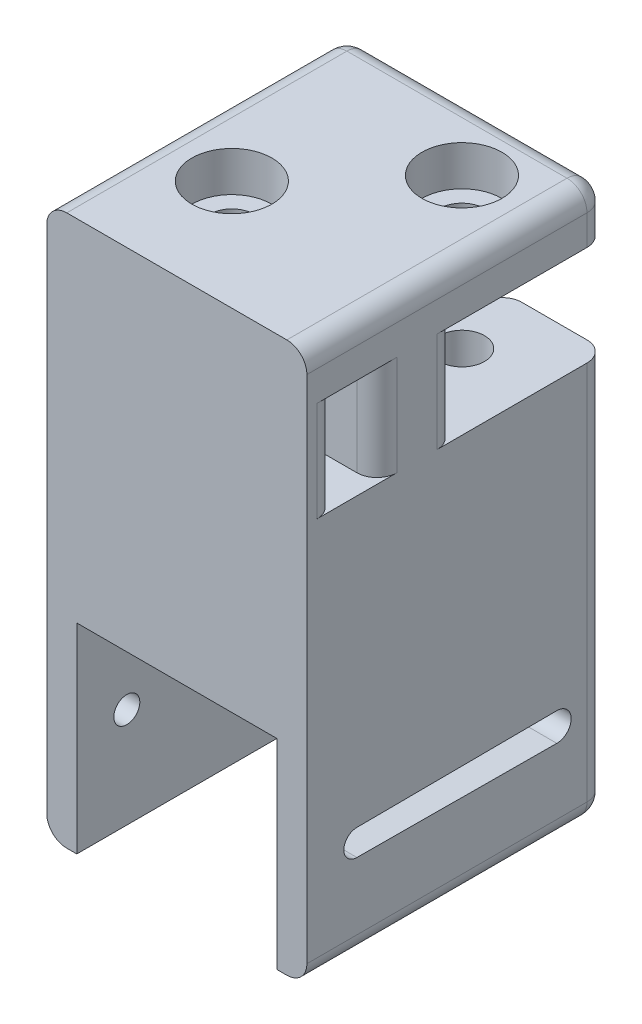
SolidWorks part; units mm, degrees
material "ABS"
ref_plane "Front Plane" through (0, 0, 0) normal (0, 0, 1) x (1, 0, 0)
ref_plane "Top Plane" through (0, 0, 0) normal (0, 1, 0) x (1, 0, 0)
ref_plane "Right Plane" through (0, 0, 0) normal (1, 0, 0) x (0, 0, -1)
sketch "Sketch2" plane through (0, 0, 0) normal (0, 1, 0) x (1, 0, 0)
  line L1 (-10, -15) -> (10, -15)
  line L2 (-10, -15) -> (-10, 15)
  line L3 (-10, 15) -> (10, 15)
  line L4 (10, -15) -> (10, 15)
  line L5 (-10, -15) -> (10, 15) construction
  line L6 (-10, 15) -> (10, -15) construction
  point P0 (0, 0)
  dimension "D1" = 20
  dimension "D2" = 30
extrude "Boss-Extrude1" add sketch "Sketch2" along normal blind 30
sketch "Sketch3" plane through (0, 30, 0) normal (0, 1, 0) x (1, 0, 0)
  line L0 (0, -15) -> (0, 15) construction
  line L1 (-10, -15) -> (10, -15) construction
  line L2 (10, 15) -> (-10, 15) construction
  line L3 (5.5, -1) -> (10, -1)
  line L4 (10, -15) -> (10, 15) construction
  line L6 (-5.5, 11) -> (-10, 11)
  line L7 (-10, 15) -> (-10, -15) construction
  line L8 (-10, 11) -> (-10, -1.3619)
  line L9 (-1.5, -8) -> (-1.5, -1.7446)
  line L10 (1.5, 4) -> (1.5, -2.2554)
  line L11 (-1.5, -8) -> (-1.5, -15)
  line L12 (1.5, -15) -> (1.5, -13.7446)
  line L13 (10, 11) -> (-5.5, 11)
  line L14 (10, 11) -> (10, 8)
  line L15 (10, 8) -> (0.2446, 8)
  line L17 (10, -15) -> (10, -1)
  line L18 (1.5, -15) -> (10, -15)
  line L19 (-5.5, -3) -> (-10, -3)
  line L20 (-10, -3) -> (-10, -1.3619)
  circle A0 centre (5.5, -8) radius 2.25
  circle A1 centre (-5.5, 4) radius 2.25
  arc A2 (5.5, -1) -> (1.5, -13.7446) centre (5.5, -8) ccw
  arc A3 (-5.5, 11) -> (-10, -1.3619) centre (-5.5, 4) cw
  line M1 (10, -15) -> (10, 15)
  line M3 (-10, 15) -> (-10, -15)
  line M4 (-10, -15) -> (10, -15)
  dimension "D3" = 4.5
  dimension "D4" = 4.5
  dimension "D7" = 7
  dimension "D8" = 7
  dimension "D1" = 5.5
  dimension "D2" = 7
  dimension "D5" = 12
  dimension "D6" = 5.5
  dimension "D9" = 3
extrude "Cut-Extrude2" cut sketch "Sketch3" against normal blind 19 contours L0 A2 L3 A0 M1 | A2 L0 | A3 L0 L6 A1 M3 | L0 A3 | L0 A2 L10 A3 | A2 L0 A3 L9 | L0 A2 L11 M4 | L0 L12 A2 M4 | L0 L15 L13 M1 | L15 L0 L13 A3 | L19 A3 M3 region at (-0.8553, 30, 12.8515) region at (0.6574, 30, 14.0101) region at (-0.6059, 30, 8) region at (0.172, 30, 8) region at (-0.8136, 30, 3.1846) region at (0.8136, 30, 0.8154) region at (-0.8157, 30, 0.9677) region at (0.6059, 30, -4) region at (-8.903, 30, 2.5203) region at (-1.3171, 30, -10.2343) region at (5.0068, 30, -9.5019)
sketch "Sketch5" plane through (0, 30, 0) normal (0, 1, 0) x (1, 0, 0)
  line L1 (10, -15) -> (-10, -15)
  line L2 (10, -15) -> (10, 15)
  line L3 (10, 15) -> (-10, 15)
  line L4 (-10, -15) -> (-10, 15)
  line L5 (10, -15) -> (-10, 15) construction
  line L6 (10, 15) -> (-10, -15) construction
  point P0 (0, 0)
extrude "Boss-Extrude2" add sketch "Sketch5" along normal blind 5
sketch "Sketch6" [suppressed] plane through (0, 30, 0) normal (0, -1, 0) x (1, 0, 0)
  line L3 (-1.5, 15) -> (10, 15) construction
  line L8 (1.5, 2.2554) -> (1.5, 15)
  line L9 (-1.5, 15) -> (10, 15) construction
  line L10 (1.5, 15) -> (10, 15)
  line L11 (10, 15) -> (10, 1)
  line L12 (10, 1) -> (5.5, 1)
  line L13 (5.5, 1) -> (10, 1) construction
  circle A0 centre (5.5, 8) radius 2.2812
  arc A1 (5.5, 1) -> (1.5, 2.2554) centre (5.5, 8) cw
extrude "Boss-Extrude3" [suppressed] add sketch "Sketch6" along normal blind 9
sketch "Sketch7" [suppressed] plane through (0, 11, 0) normal (0, 1, 0) x (1, 0, 0)
  line L0 (0.2446, 8) -> (-10, 8)
  line L1 (-5.5, -3) -> (-10, -3)
  line L2 (-10, 11) -> (-10, -3) construction
  line L3 (-1.5, -15) -> (-1.5, -1.7446) construction
  line L4 (-1.5, -1.7446) -> (-1.5, -8)
  line L5 (1.5, -2.2554) -> (1.5, 4)
  line L6 (1.5, 4) -> (1.5, -2.2554) construction
  line L7 (-10, 8) -> (-10, -3)
  arc A0 (0.2446, 8) -> (1.5, 4) centre (-5.5, 4) cw
  arc A1 (-1.5, -1.7446) -> (-5.5, -3) centre (-5.5, 4) cw
  arc A2 (-5.5, -3) -> (-1.5, -1.7446) centre (-5.5, 4) ccw construction
  arc A3 (1.5, -2.2554) -> (-1.5, -8) centre (5.5, -8) ccw
  circle A4 centre (-5.5, 4) radius 2.25
  arc A5 (-5.5, -3) -> (-1.5, -1.7446) centre (-5.5, 4) ccw construction
  arc M1 (-5.5, -3) -> (-1.5, -1.7446) centre (-5.5, 4) ccw
  line M2 (-1.5, -1.7446) -> (-1.5, -15)
  line M7 (1.5, -2.2554) -> (1.5, 4)
  arc M8 (1.5, 4) -> (0.2446, 8) centre (-5.5, 4) ccw
  line M9 (0.2446, 8) -> (10, 8)
  line M11 (10, 11) -> (-10, 11)
  line M12 (-10, 11) -> (-10, -3)
  circle M14 centre (-5.5, 4) radius 2.25
extrude "Boss-Extrude4" [suppressed] add sketch "Sketch7" along normal blind 9 contours A3 L0 M7 M8 M9 M11 M12 M1 M2 M14
sketch "Sketch15" [suppressed] plane through (0, 30, 0) normal (0, -1, 0) x (1, 0, 0)
  line L0 (10, -11) -> (-10, -11) construction
  line L5 (10, -8) -> (10, -11)
  line L6 (10, -11) -> (-5.5, -11)
  line L7 (0.2446, -8) -> (10, -8)
  arc A0 (0.2446, -8) -> (-5.5, -11) centre (-5.5, -4) cw
extrude "Boss-Extrude6" [suppressed] add sketch "Sketch15" along normal blind 9
sketch "Sketch16" plane through (0, 11, 0) normal (0, 1, 0) x (1, 0, 0)
  line L0 (10, -15) -> (10, -1)
  line L1 (10, -1) -> (5.5, -1)
  line L2 (10, -15) -> (1.5, -15)
  line L3 (-1.5, -15) -> (10, -15) construction
  line L4 (1.5, -15) -> (1.5, -2.2554)
  circle A0 centre (5.5, -8) radius 2.25
  arc A1 (5.5, -1) -> (1.5, -2.2554) centre (5.5, -8) ccw construction
  arc A2 (1.5, -2.2554) -> (5.5, -1) centre (5.5, -8) cw
  arc M2 (5.5, -1) -> (1.5, -2.2554) centre (5.5, -8) ccw
  line M4 (-1.5, -15) -> (10, -15)
  line M5 (10, -15) -> (10, -1)
  line M6 (10, -1) -> (5.5, -1)
  circle M7 centre (5.5, -8) radius 2.25
  dimension "D1" = 3
extrude "Boss-Extrude7" add sketch "Sketch16" along normal blind 9 contours L4 M4 M5 M6 M2 M7 region at (5.75, 11, 14.8362)
sketch "Sketch17" plane through (0, 30, 0) normal (0, -1, 0) x (1, 0, 0)
  line L0 (0.2446, -8) -> (-10, -8)
  line L1 (-10, -11) -> (-10, 3) construction
  line L2 (-10, -8) -> (-10, 3)
  line L3 (1.5, -4) -> (1.5, 2.2554) construction
  line L4 (1.5, -4) -> (1.5, 2.2554)
  line L5 (-1.5, 8.0934) -> (-1.5, 1.7446)
  line L6 (-1.5, 15) -> (-1.5, 1.7446) construction
  line L7 (-5.5, 3) -> (-10, 3)
  line L8 (-5.5, 3) -> (-10, 3) construction
  circle A0 centre (-5.5, -4) radius 2.25
  arc A1 (-1.5, 1.7446) -> (-5.5, 3) centre (-5.5, -4) ccw
  arc A2 (-1.5, 1.7446) -> (-5.5, 3) centre (-5.5, -4) ccw construction
  arc A3 (0.2446, -8) -> (1.5, -4) centre (-5.5, -4) ccw
  arc A4 (1.5, 2.2554) -> (-1.5, 8) centre (5.5, 8) cw
  arc A5 (-1.5, 1.7446) -> (-5.5, 3) centre (-5.5, -4) ccw construction
  circle M1 centre (-5.5, -4) radius 2.25
  line M2 (-10, 3) -> (-10, -11)
  arc M6 (0.2446, -8) -> (1.5, -4) centre (-5.5, -4) ccw
  line M7 (1.5, -4) -> (1.5, 2.2554)
  arc M13 (-1.5, 1.7446) -> (-5.5, 3) centre (-5.5, -4) ccw
extrude "Boss-Extrude8" add sketch "Sketch17" along normal blind 9 contours A4 L5 L0 M7 M13 M2 M6 M1 region at (-4.0921, 30, -2.1111)
sketch "Sketch18" plane through (0, 11, 0) normal (0, 1, 0) x (1, 0, 0)
  line L0 (10, 11) -> (10, 8)
  line L1 (10, 8) -> (0.2446, 8)
  line L2 (10, 11) -> (-10, 11) construction
  line L3 (10, 11) -> (-5.5, 11)
  arc A0 (0.2446, 8) -> (-5.5, 11) centre (-5.5, 4) ccw
extrude "Boss-Extrude9" add sketch "Sketch18" along normal blind 9
sketch "Sketch9" [suppressed] plane through (0, 0, -15) normal (0, 0, -1) x (-1, 0, 0)
  line L0 (-10, 0) -> (10, 0) construction
  line L1 (-5.5, 3) -> (5.5, 3)
  line L2 (-5.5, 3) -> (-5.5, 0)
  line L3 (-5.5, 0) -> (5.5, 0)
  line L4 (5.5, 3) -> (5.5, 0)
  line L5 (-5.5, 3) -> (5.5, 0) construction
  line L6 (-5.5, 0) -> (5.5, 3) construction
  line L9 (-10, 35) -> (-10, 0) construction
  point P0 (0, 1.5)
  dimension "D1" = 3
  dimension "D2" = 11
  dimension "D3" = 4.5
extrude "Boss-Extrude5" [suppressed] add sketch "Sketch9" along normal blind 7
sketch "Sketch10" [suppressed] plane through (0, 3, 0) normal (0, 1, 0) x (1, 0, 0)
  line L0 (-5.5, 15) -> (5.5, 15) construction
  circle A0 centre (0, 18.5) radius 1.75
  dimension "D1" = 3.5
  dimension "D2" = 3.5
extrude "Cut-Extrude4" [suppressed] cut sketch "Sketch10" against normal through all
sketch "Sketch11" [suppressed] plane through (0, 3, 0) normal (0, 1, 0) x (1, 0, 0)
  circle A0 centre (0, 18.5) radius 3
  dimension "D1" = 6
extrude "Cut-Extrude5" [suppressed] cut sketch "Sketch11" against normal blind 1
sketch "Sketch8" plane through (0, 35, 0) normal (0, 1, 0) x (1, 0, 0)
  line L0 (0, -15) -> (0, 15) construction
  line L1 (-10, -15) -> (10, -15) construction
  line L2 (10, 15) -> (-10, 15) construction
  circle A0 centre (5.5, -8) radius 2.25
  circle A1 centre (-5.5, 4) radius 2.25
  dimension "D1" = 4.5
  dimension "D2" = 4.5
  dimension "D3" = 7
  dimension "D4" = 5.5
  dimension "D5" = 5.5
  dimension "D6" = 12
extrude "Cut-Extrude3" cut sketch "Sketch8" against normal through all
hole_wizard "CBORE for M4 Hex Socket Head Cap Screw1" positions "Sketch12" profile "Sketch13" counterbore size "M4" standard "ISO" end condition up to next
sketch "Sketch12" plane through (0, 35, 0) normal (0, 1, 0) x (1, 0, 0)
  point P0 (5.5, -8)
  point P3 (-5.5, 4)
sketch "Sketch13" plane through (5.5, 35, 8) normal (1, 0, 0) x (0, 0, 1)
  line L0 (0, 0) -> (0, 35)
  line L1 (0, 35) -> (2.25, 35)
  line L3 (2.25, 35) -> (2.25, 4)
  line L4 (2.25, 4) -> (4, 4)
  line L5 (4, 4) -> (4, 0)
  line L7 (4, 0) -> (0, 0)
  line L11 (0, -6.35) -> (0, 107.95) construction
  dimension "Thru Hole Dia." = 4.5
  dimension "Thru Hole Depth" = 35
  dimension "C'Bore Dia." = 8
  dimension "C'Bore Depth" = 4
sketch "Sketch14" plane through (0, 0, 0) normal (0, -1, 0) x (1, 0, 0)
  line L1 (5.5, 3.8142) -> (9.125, 5.9071)
  line L2 (9.125, 5.9071) -> (9.125, 10.0929)
  line L3 (9.125, 10.0929) -> (5.5, 12.1858)
  line L4 (5.5, 12.1858) -> (1.875, 10.0929)
  line L5 (1.875, 10.0929) -> (1.875, 5.9071)
  line L6 (1.875, 5.9071) -> (5.5, 3.8142)
  line L7 (-5.5, -8.1858) -> (-1.875, -6.0929)
  line L8 (-1.875, -6.0929) -> (-1.875, -1.9071)
  line L9 (-1.875, -1.9071) -> (-5.5, 0.1858)
  line L10 (-5.5, 0.1858) -> (-9.125, -1.9071)
  line L11 (-9.125, -1.9071) -> (-9.125, -6.0929)
  line L12 (-9.125, -6.0929) -> (-5.5, -8.1858)
  circle A0 centre (5.5, 8) radius 3.625 construction
  circle A1 centre (-5.5, -4) radius 3.625 construction
  dimension "D1" = 7.25
  dimension "D2" = 7.25
extrude "Cut-Extrude6" cut sketch "Sketch14" against normal blind 10
sketch "Sketch21" plane through (0, 20, 0) normal (0, 1, 0) x (1, 0, 0)
  line L3 (10, 0) -> (5.5, 0)
  line L4 (10, -15) -> (-2.5, -15)
  line L5 (-2.5, -15) -> (-2.5, -8)
  line L6 (10, -15) -> (10, 0)
  arc A0 (5.5, 0) -> (-2.5, -8) centre (5.5, -8) ccw
  dimension "D1" = 8
extrude "Cut-Extrude8" cut sketch "Sketch21" along normal blind 10
sketch "Sketch23" plane through (0, 11, 0) normal (0, 1, 0) x (1, 0, 0)
  line L36 (-11, 12) -> (-11, -4)
  line L37 (-11, -4) -> (-5.5, -4)
  line L38 (-2.5, -3.4162) -> (-2.5, -16)
  line L39 (-2.5, -16) -> (2.5, -16)
  line L40 (2.5, -16) -> (2.5, 4)
  line L41 (-5.5, 12) -> (-11, 12)
  line L42 (-11, 12) -> (-11, -4)
  line L43 (-11, -4) -> (-5.5, -4)
  line L44 (-2.5, -3.4162) -> (-2.5, -16)
  line L45 (-2.5, -16) -> (2.5, -16)
  line L46 (2.5, -16) -> (2.5, 4)
  line L47 (-5.5, 12) -> (-11, 12)
  arc A12 (-5.5, -4) -> (-2.5, -3.4162) centre (-5.5, 4) ccw
  arc A13 (2.5, 4) -> (-5.5, 12) centre (-5.5, 4) ccw
  arc A14 (-5.5, -4) -> (-2.5, -3.4162) centre (-5.5, 4) ccw
  arc A15 (2.5, 4) -> (-5.5, 12) centre (-5.5, 4) ccw
  dimension "D1" = 1
extrude "Cut-Extrude9" cut sketch "Sketch23" along normal blind 10
sketch "Sketch27" plane through (-10, 0, 0) normal (-1, 0, 0) x (0, 0, 1)
  line L0 (-12, 21) -> (-12, 11) construction
  line L1 (-8, 30) -> (-12, 30)
  line L2 (-8, 30) -> (-8, 20)
  line L3 (-8, 20) -> (-12, 20)
  line L4 (-12, 30) -> (-12, 20)
  dimension "D1" = 10
extrude "Cut-Extrude13" cut sketch "Sketch27" against normal through all
sketch "Sketch24" [suppressed] plane through (0, 11, 0) normal (0, 1, 0) x (1, 0, 0)
  line L16 (-2.5, -16) -> (11, -16)
  line L17 (11, -16) -> (11, 0)
  line L18 (11, 0) -> (5.5, 0)
  line L19 (-2.5, -8) -> (-2.5, -16)
  line L20 (-2.5, -16) -> (11, -16)
  line L21 (11, -16) -> (11, 0)
  line L22 (11, 0) -> (5.5, 0)
  line L23 (-2.5, -8) -> (-2.5, -16)
  arc A6 (5.5, 0) -> (-2.5, -8) centre (5.5, -8) ccw
  arc A7 (5.5, 0) -> (-2.5, -8) centre (5.5, -8) ccw
  dimension "D1" = 1
extrude "Cut-Extrude10" [suppressed] cut sketch "Sketch24" along normal blind 10
sketch "Sketch25" [suppressed] plane through (0, 30, 0) normal (0, -1, 0) x (1, 0, 0)
  line L4 (-10, -12) -> (-10, 4)
  line L5 (2.5, -4) -> (2.5, 15)
  line L6 (-10, -12) -> (-5.5, -12)
  line L7 (2.5, -4) -> (2.5, 15)
  line L8 (-10, -12) -> (-5.5, -12)
  line L9 (-5.5, 4) -> (-10, 4)
  line L10 (-5.5, 4) -> (-10, 4)
  line L13 (2.5, 15) -> (-2.5, 15)
  line L15 (-2.5, 15) -> (-2.5, 3.4162)
  arc A4 (-5.5, -12) -> (2.5, -4) centre (-5.5, -4) ccw
  arc A5 (-5.5, -12) -> (2.5, -4) centre (-5.5, -4) ccw
  arc A7 (-5.5, 4) -> (-2.5, 3.4162) centre (-5.5, -4) cw
  arc A8 (-0.9286, 2.5652) -> (-5.5, 4) centre (-5.5, -4) ccw
  dimension "D3" = 5
  dimension "D1" = 1
  dimension "D2" = 1
extrude "Cut-Extrude11" [suppressed] cut sketch "Sketch25" along normal blind 10
sketch "Sketch26" [suppressed] plane through (-10, 0, 0) normal (-1, 0, 0) x (0, 0, 1)
  line L0 (-12, 20) -> (-12, 30) construction
  line L1 (-8, 11) -> (-12, 11)
  line L2 (-8, 11) -> (-8, 21)
  line L3 (-8, 21) -> (-12, 21)
  line L4 (-12, 11) -> (-12, 21)
  dimension "D1" = 10
extrude "Cut-Extrude12" [suppressed] cut sketch "Sketch26" against normal through all
sketch "Sketch28" plane through (-10, 0, 0) normal (-1, 0, 0) x (0, 0, 1)
  line L0 (-15, 35) -> (15, 35) construction
  line L2 (-15, 35) -> (-15, 0) construction
  line L3 (-15, 35) -> (15, 35)
  line L4 (15, 35) -> (15, 0)
  line L5 (-15, 35) -> (-15, 0)
  line L6 (-12, 30) -> (-12, 11)
  line L7 (-8, 30) -> (-12, 30)
  line L10 (4, 11) -> (4, 21)
  line L11 (-12, 11) -> (4, 11)
  line L12 (-12, 30) -> (-12, 11)
  line L13 (-8, 30) -> (-12, 30)
  line L16 (4, 11) -> (4, 21)
  line L17 (-12, 11) -> (4, 11)
  line L18 (-15, 0) -> (15, 0)
  line L19 (-15, 0) -> (15, 0) construction
  line L23 (-8, 21) -> (-8, 30)
  line L24 (-8, 21) -> (-8, 30)
  line L25 (4, 21) -> (-8, 21)
  line L26 (4, 21) -> (-8, 21)
  dimension "D1" = 0
extrude "Boss-Extrude11" add sketch "Sketch28" along normal blind 3
sketch "Sketch30" plane through (10, 0, 0) normal (1, 0, 0) x (0, 0, -1)
  line L0 (-15, 35) -> (15, 35) construction
  line L1 (8, 30) -> (12, 30) construction
  line L2 (12, 30) -> (12, 20) construction
  line L3 (8, 20) -> (12, 20) construction
  line L4 (8, 20) -> (8, 30) construction
  line L5 (15, 35) -> (15, 0) construction
  line L6 (-15, 20) -> (0, 20) construction
  line L7 (0, 30) -> (0, 20) construction
  line L8 (-15, 30) -> (0, 30) construction
  line L9 (-15, 35) -> (-15, 30) construction
  line L10 (-15, 35) -> (15, 35)
  line L11 (8, 30) -> (12, 30)
  line L12 (12, 30) -> (12, 20)
  line L13 (8, 20) -> (12, 20)
  line L14 (8, 20) -> (8, 30)
  line L15 (15, 35) -> (15, 0)
  line L16 (-15, 20) -> (0, 20)
  line L17 (0, 30) -> (0, 20)
  line L18 (-15, 30) -> (0, 30)
  line L19 (-15, 35) -> (-15, 30)
  line L20 (-15, 20) -> (-15, 0)
  line L21 (-15, 0) -> (15, 0) construction
  line L22 (-15, 0) -> (15, 0)
extrude "Boss-Extrude13" add sketch "Sketch30" along normal blind 3
sketch "Sketch32" [suppressed] plane through (-10, 0, 0) normal (-1, 0, 0) x (0, 0, 1)
  line L0 (-15, 35) -> (15, 35) construction
  line L1 (-15, 35) -> (-15, 0) construction
  line L2 (-12, 11) -> (-8, 11) construction
  line L3 (-8, 20) -> (-8, 11) construction
  line L4 (-12, 11) -> (-12, 30) construction
  line L5 (-12, 30) -> (4, 30) construction
  line L6 (4, 20) -> (4, 30) construction
  line L7 (-8, 20) -> (4, 20) construction
  line L8 (-15, 35) -> (15, 35)
  line L9 (-15, 35) -> (-15, 0)
  line L10 (-12, 11) -> (-8, 11)
  line L11 (-8, 20) -> (-8, 11)
  line L12 (-12, 11) -> (-12, 30)
  line L13 (-12, 30) -> (4, 30)
  line L14 (4, 20) -> (4, 30)
  line L15 (-8, 20) -> (4, 20)
  line L16 (15, 35) -> (15, 0)
  line L17 (-15, 0) -> (15, 0) construction
  line L18 (15, 0) -> (-15, 0)
extrude "Boss-Extrude15" [suppressed] add sketch "Sketch32" along normal blind 3
sketch "Sketch33" [suppressed] plane through (10, 0, 0) normal (1, 0, 0) x (0, 0, -1)
  line L0 (8, 11) -> (12, 11) construction
  line L1 (8, 11) -> (8, 21) construction
  line L2 (12, 21) -> (12, 11) construction
  line L3 (12, 21) -> (8, 21) construction
  line L4 (15, 35) -> (15, 0) construction
  line L5 (-15, 35) -> (15, 35) construction
  line L6 (-15, 11) -> (0, 11) construction
  line L7 (0, 11) -> (0, 21) construction
  line L8 (0, 21) -> (-15, 21) construction
  line L9 (-15, 35) -> (-15, 21) construction
  line L10 (8, 11) -> (12, 11)
  line L11 (8, 11) -> (8, 21)
  line L12 (12, 21) -> (12, 11)
  line L13 (12, 21) -> (8, 21)
  line L14 (15, 35) -> (15, 0)
  line L15 (-15, 35) -> (15, 35)
  line L16 (-15, 11) -> (0, 11)
  line L17 (0, 11) -> (0, 21)
  line L18 (0, 21) -> (-15, 21)
  line L19 (-15, 35) -> (-15, 21)
  line L20 (-15, 11) -> (-15, 0)
  line L21 (-15, 0) -> (15, 0) construction
  line L22 (-15, 0) -> (15, 0)
extrude "Boss-Extrude16" [suppressed] add sketch "Sketch33" along normal blind 3
sketch "Sketch29" plane through (0, 0, 0) normal (0, -1, 0) x (1, 0, 0)
  line L0 (13, -15) -> (-13, -15) construction
  line L1 (-13, 15) -> (-10, 15)
  line L2 (-13, 15) -> (-13, -15)
  line L3 (-13, -15) -> (-10, -15)
  line L4 (-10, 15) -> (-10, -15)
  dimension "D1" = 3
extrude "Boss-Extrude12" add sketch "Sketch29" along normal blind 20
sketch "Sketch31" plane through (0, 0, 0) normal (0, -1, 0) x (1, 0, 0)
  line L0 (13, -15) -> (-10, -15) construction
  line L1 (13, 15) -> (10, 15)
  line L2 (13, 15) -> (13, -15)
  line L3 (13, -15) -> (10, -15)
  line L4 (10, 15) -> (10, -15)
  dimension "D1" = 3
extrude "Boss-Extrude14" add sketch "Sketch31" along normal blind 20
sketch "Sketch34" [suppressed] plane through (0, 0, 0) normal (0, -1, 0) x (1, 0, 0)
  line L0 (13, -15) -> (-13, -15) construction
  line L1 (-13, 15) -> (-10, 15)
  line L2 (-13, 15) -> (-13, -15)
  line L3 (-13, -15) -> (-10, -15)
  line L4 (-10, 15) -> (-10, -15)
extrude "Boss-Extrude17" [suppressed] add sketch "Sketch34" along normal blind 20
sketch "Sketch35" [suppressed] plane through (0, 0, 0) normal (0, -1, 0) x (1, 0, 0)
  line L0 (13, -15) -> (-10, -15) construction
  line L1 (13, 15) -> (10, 15)
  line L2 (13, 15) -> (13, -15)
  line L3 (13, -15) -> (10, -15)
  line L4 (10, 15) -> (10, -15)
  dimension "D1" = 3
extrude "Boss-Extrude18" [suppressed] add sketch "Sketch35" along normal blind 20
sketch "Sketch36" plane through (-13, 0, 0) normal (-1, 0, 0) x (0, 0, 1)
  line L0 (-15, 0) -> (15, 0) construction
  line L1 (15, -20) -> (15, 35) construction
  line L2 (-15, 35) -> (-15, -20) construction
  circle A0 centre (-10, -10) radius 1.3011
  circle A1 centre (10, -10) radius 1.4145
  dimension "D1" = 10
  dimension "D2" = 10
  dimension "D3" = 5
  dimension "D4" = 5
extrude "Cut-Extrude14" cut sketch "Sketch36" against normal through all
sketch "Sketch37" [suppressed] plane through (-13, 0, 0) normal (-1, 0, 0) x (0, 0, 1)
  line L0 (-15, 0) -> (15, 0) construction
  line L1 (-15, 35) -> (-15, -20) construction
  line L2 (15, -20) -> (15, 35) construction
  circle A0 centre (-10, -10) radius 1.75
  circle A1 centre (10, -10) radius 1.75
  dimension "D3" = 3.5
  dimension "D5" = 3.5
  dimension "D1" = 10
  dimension "D2" = 5
  dimension "D4" = 5
extrude "Cut-Extrude15" [suppressed] cut sketch "Sketch37" against normal through all
mirror "Mirror1" about plane through (-10, 30, 15) normal (0, 0, -1) of bodies 137 113
delete or keep bodies "Body-Delete/Keep 1" type keep bodies bodies 116
fillet "Fillet1-r" [suppressed] radius 2
fillet "Fillet2-r" [suppressed] radius 2
fillet "Fillet3-r" [suppressed] radius 2
fillet "Fillet4-l" radius 2 10 edges at (0, 35, 15) (-13, 35, 30) (13, 35, 30) (13, 32.5, 15) (-13, 7.5, 15) (13, 0, 15) (-11.5, -20, 15) (-13, -20, 30) (11.5, -20, 15) (13, -20, 30)
fillet "Fillet5-l" radius 2 9 edges at (2.5, 15.5, 15) (-2.5, 20.5, 15) (-2.5, 16, 26.5838) (13, 25, 30) (13, 25, 38) (13, 25, 42) (-13, 20.5, 42) (-13, 16, 26) (-13, 25.5, 38)
sketch "Sketch38" plane through (13, 0, 0) normal (1, 0, 0) x (0, 0, -1)
  line L0 (-40, -8.6989) -> (-20, -8.5855)
  line L1 (-20, -8.5855) -> (-20, -11.4145)
  line L2 (-20, -11.4145) -> (-40, -11.3011)
  line L3 (-40, -11.3011) -> (-40, -8.6989)
  circle A0 centre (-40, -10) radius 1.3011 construction
  circle A1 centre (-20, -10) radius 1.4145 construction
extrude "Cut-Extrude16" cut sketch "Sketch38" against normal up to next
